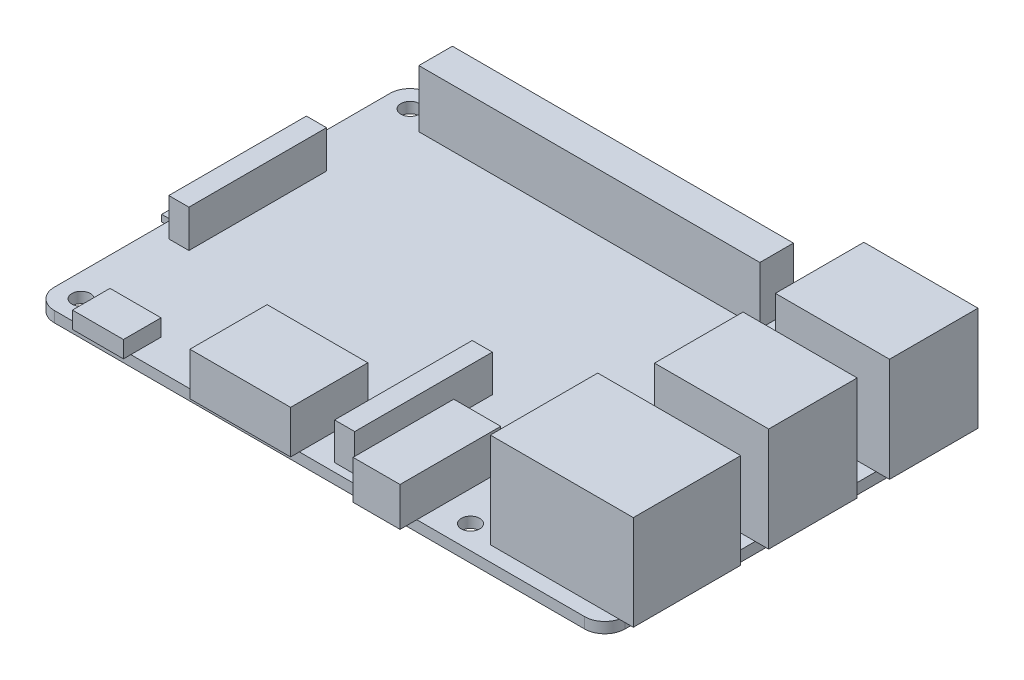
SolidWorks part; units mm, degrees
ref_plane "Front Plane" through (0, 0, 0) normal (0, 0, 1) x (1, 0, 0)
ref_plane "Top Plane" through (0, 0, 0) normal (0, 1, 0) x (1, 0, 0)
ref_plane "Right Plane" through (0, 0, 0) normal (1, 0, 0) x (0, 0, -1)
sketch "Sketch2" plane through (0, 0, 0) normal (0, 1, 0) x (1, 0, 0)
  line L1 (3, 0) -> (82, 0)
  line L2 (0, 3) -> (0, 53)
  line L3 (3, 56) -> (82, 56)
  line L4 (85, 3) -> (85, 53)
  arc A0 (82, 0) -> (85, 3) centre (82, 3) ccw
  arc A1 (82, 56) -> (85, 53) centre (82, 53) cw
  arc A2 (0, 53) -> (3, 56) centre (3, 53) cw
  arc A3 (3, 0) -> (0, 3) centre (3, 3) cw
  point P13 (0, 0)
  dimension "D3" = 3
  dimension "D1" = 85
  dimension "D2" = 56
extrude "PCB" add sketch "Sketch2" along normal blind 1.6
hole_wizard "Mount Holes" positions "Sketch4" profile "Sketch3" hole size "Ø2.7" standard "ANSI Metric" end condition through all
sketch "Sketch4" plane through (0, 1.6, 0) normal (0, 1, 0) x (1, 0, 0)
  line L0 (0, 53) -> (0, 3) construction
  line L1 (3, 0) -> (82, 0) construction
  point P0 (3.5, 3.5)
  point P2 (3.5, 52.5)
  point P4 (61.5, 52.5)
  point P6 (61.5, 3.5)
  dimension "D1" = 3.5
  dimension "D2" = 58
  dimension "D3" = 3.5
  dimension "D4" = 49
sketch "Sketch3" plane through (3.5, 1.6, -3.5) normal (1, 0, 0) x (0, 0, 1)
  line L0 (0, 0) -> (0, 1.6)
  line L1 (0, 1.6) -> (1.375, 1.6)
  line L2 (1.375, 1.6) -> (1.375, 0)
  line L5 (1.375, 0) -> (0, 0)
  line L11 (0, -6.35) -> (0, 107.95) construction
  dimension "Thru Hole Dia." = 2.75
  dimension "Thru Hole Depth" = 1.6
sketch "Sketch5" plane through (0, 1.6, 0) normal (0, 1, 0) x (1, 0, 0)
  line L0 (3, 0) -> (82, 0) construction
  line L1 (70, 40.41) -> (87, 40.41)
  line L2 (70, 40.41) -> (70, 53.59)
  line L3 (70, 53.59) -> (87, 53.59)
  line L4 (87, 40.41) -> (87, 53.59)
  line L5 (70, 35.59) -> (87, 35.59)
  line L6 (70, 35.59) -> (70, 22.41)
  line L7 (70, 22.41) -> (87, 22.41)
  line L8 (87, 35.59) -> (87, 22.41)
  line L9 (85, 3) -> (85, 53) construction
  point P8 (70, 29)
  point P9 (70, 47)
  dimension "D1" = 29
  dimension "D2" = 47
  dimension "D3" = 13.18
  dimension "D4" = 17
  dimension "D5" = 2
extrude "USB Host" add sketch "Sketch5" along normal blind 15.5
sketch "Sketch6" plane through (0, 1.6, 0) normal (0, 1, 0) x (1, 0, 0)
  line L0 (85, 3) -> (85, 22.41) construction
  line L1 (65.7, 2.25) -> (87, 2.25)
  line L2 (65.7, 2.25) -> (65.7, 18.25)
  line L3 (65.7, 18.25) -> (87, 18.25)
  line L4 (87, 2.25) -> (87, 18.25)
  line L5 (3, 0) -> (82, 0) construction
  point P6 (65.7, 10.25)
  dimension "D1" = 2
  dimension "D2" = 16
  dimension "D3" = 10.25
  dimension "D4" = 21.3
extrude "Ethernet" add sketch "Sketch6" along normal blind 14.15
sketch "Sketch7" plane through (0, 1.6, 0) normal (0, 1, 0) x (1, 0, 0)
  line L0 (3, 0) -> (82, 0) construction
  line L1 (43.5, 21.75) -> (46.5, 21.75)
  line L2 (43.5, 21.75) -> (43.5, 1.25)
  line L3 (43.5, 1.25) -> (46.5, 1.25)
  line L4 (46.5, 21.75) -> (46.5, 1.25)
  line L5 (43.5, 21.75) -> (46.5, 1.25) construction
  line L6 (43.5, 1.25) -> (46.5, 21.75) construction
  line L7 (0, 53) -> (0, 3) construction
  point P0 (45, 11.5)
  dimension "D1" = 20.5
  dimension "D2" = 3
  dimension "D3" = 11.5
  dimension "D4" = 45
extrude "Camera Connector" add sketch "Sketch7" along normal blind 5.5
sketch "Sketch9" plane through (0, 1.6, 0) normal (0, 1, 0) x (1, 0, 0)
  line L0 (0, 53) -> (0, 3) construction
  line L1 (3, 0) -> (82, 0) construction
  line L2 (24.5, 10.2) -> (39.5, 10.2)
  line L3 (24.5, 10.2) -> (24.5, -1.3)
  line L4 (24.5, -1.3) -> (39.5, -1.3)
  line L5 (39.5, 10.2) -> (39.5, -1.3)
  line L6 (24.5, 10.2) -> (39.5, -1.3) construction
  line L7 (24.5, -1.3) -> (39.5, 10.2) construction
  point P1 (32, 4.45)
  dimension "D1" = 15
  dimension "D2" = 11.5
  dimension "D3" = 32
  dimension "D4" = 1.3
extrude "HDMI" add sketch "Sketch9" along normal blind 6.4
sketch "Sketch10" plane through (0, 1.6, 0) normal (0, 1, 0) x (1, 0, 0)
  line L0 (0, 53) -> (0, 3) construction
  line L1 (50, 12.5) -> (57, 12.5)
  line L2 (50, 12.5) -> (50, -2.5)
  line L3 (50, -2.5) -> (57, -2.5)
  line L4 (57, 12.5) -> (57, -2.5)
  line L5 (50, 12.5) -> (57, -2.5) construction
  line L6 (50, -2.5) -> (57, 12.5) construction
  line L7 (39.5, 0) -> (82, 0) construction
  point P0 (53.5, 5)
  dimension "D1" = 53.5
  dimension "D2" = 7
  dimension "D3" = 15
  dimension "D4" = 2.5
extrude "AV" add sketch "Sketch10" along normal blind 5.8
sketch "Sketch12" plane through (0, 1.6, 0) normal (0, 1, 0) x (1, 0, 0)
  line L0 (0, 53) -> (0, 3) construction
  line L1 (6.8, 4.5) -> (14.4, 4.5)
  line L2 (6.8, 4.5) -> (6.8, -1.1)
  line L3 (6.8, -1.1) -> (14.4, -1.1)
  line L4 (14.4, 4.5) -> (14.4, -1.1)
  line L5 (6.8, 4.5) -> (14.4, -1.1) construction
  line L6 (6.8, -1.1) -> (14.4, 4.5) construction
  line L7 (3, 0) -> (24.5, 0) construction
  point P0 (10.6, 1.7)
  dimension "D1" = 5.6
  dimension "D2" = 7.6
  dimension "D3" = 10.6
  dimension "D4" = 1.1
extrude "USB-Micro" add sketch "Sketch12" along normal blind 2.5
sketch "Sketch13" plane through (0, 1.6, 0) normal (0, 1, 0) x (1, 0, 0)
  line L1 (2.3, 38.25) -> (5.3, 38.25)
  line L2 (2.3, 38.25) -> (2.3, 17.75)
  line L3 (2.3, 17.75) -> (5.3, 17.75)
  line L4 (5.3, 38.25) -> (5.3, 17.75)
  line L5 (2.3, 38.25) -> (5.3, 17.75) construction
  line L6 (2.3, 17.75) -> (5.3, 38.25) construction
  line L7 (14.4, 0) -> (24.5, 0) construction
  line L8 (0, 53) -> (0, 3) construction
  point P0 (3.8, 28)
  dimension "D1" = 2.3
  dimension "D2" = 28
  dimension "D3" = 20.5
  dimension "D4" = 3
extrude "Display" add sketch "Sketch13" along normal blind 5.6
sketch "Sketch14" plane through (0, 1.6, 0) normal (0, 1, 0) x (1, 0, 0)
  line L0 (0, 53) -> (0, 3) construction
  line L1 (7.1, 55.2) -> (57.9, 55.2)
  line L2 (7.1, 55.2) -> (7.1, 50.2)
  line L3 (7.1, 50.2) -> (57.9, 50.2)
  line L4 (57.9, 55.2) -> (57.9, 50.2)
  line L5 (7.1, 55.2) -> (57.9, 50.2) construction
  line L6 (7.1, 50.2) -> (57.9, 55.2) construction
  line L7 (82, 56) -> (3, 56) construction
  point P0 (32.5, 52.7)
  dimension "D1" = 32.5
  dimension "D2" = 50.8
  dimension "D3" = 5
  dimension "D4" = 0.8
extrude "GPIO" add sketch "Sketch14" along normal blind 8.54
sketch "Sketch15" plane through (0, 0, 0) normal (0, -1, 0) x (1, 0, 0)
  line L0 (3, 0) -> (82, 0) construction
  line L1 (0, -53) -> (0, -3) construction
  line L2 (14, -33) -> (-3, -33)
  line L3 (14, -33) -> (14, -22)
  line L4 (14, -22) -> (-3, -22)
  line L5 (-3, -33) -> (-3, -22)
  line L6 (14, -33) -> (-3, -22) construction
  line L7 (14, -22) -> (-3, -33) construction
  point P1 (5.5, -27.5)
  dimension "D1" = 11
  dimension "D2" = 22
  dimension "D3" = 3
  dimension "D4" = 17
extrude "uSD Card" add sketch "Sketch15" along normal blind 1
sketch "Cable Reference" plane through (0, 7.1, 0) normal (0, 1, 0) x (1, 0, 0)
  line L0 (43.5, 11.5) -> (46.5, 11.5) construction
  line L1 (43.5, 21.75) -> (43.5, 1.25) construction
  line L2 (46.5, 1.25) -> (46.5, 21.75) construction
  line L3 (45, 3.5) -> (45, 19.5) construction
  point P8 (45, 11.5)
  dimension "D1" = 16
